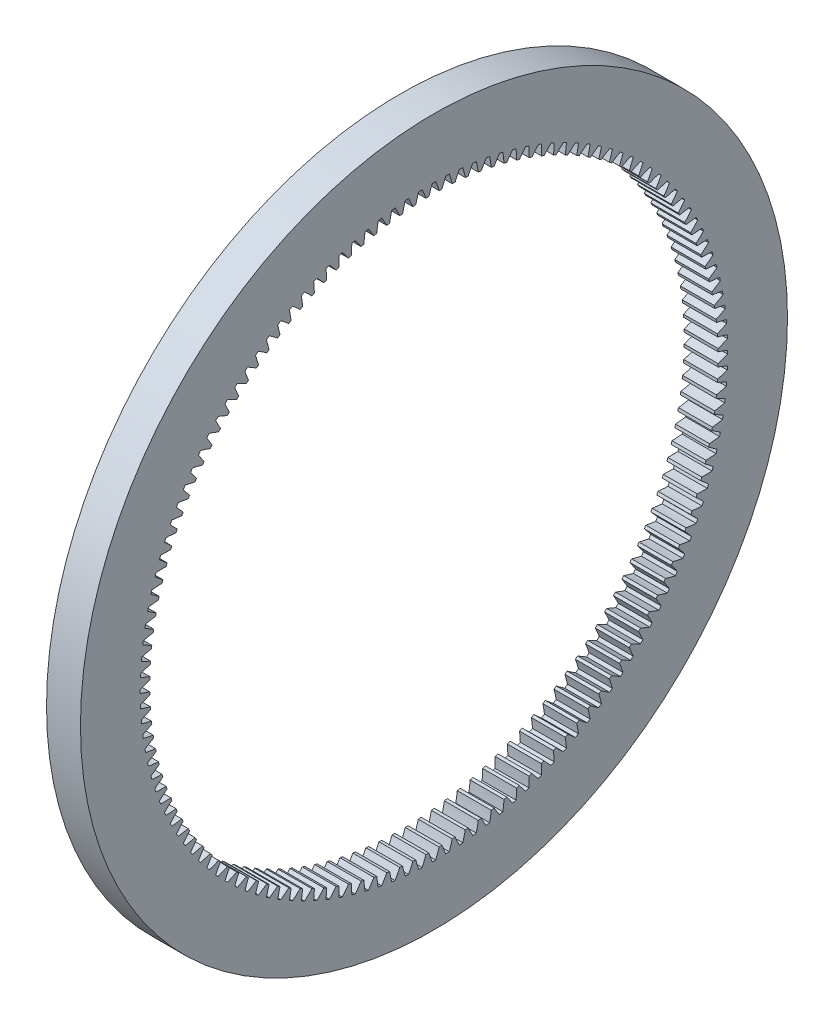
SolidWorks part; units mm, degrees
ref_plane "Plane1" through (0, 0, 0) normal (0, 0, 1) x (1, 0, 0)
ref_plane "Plane2" through (0, 0, 0) normal (0, 1, 0) x (1, 0, 0)
ref_plane "Plane3" through (0, 0, 0) normal (1, 0, 0) x (0, 0, -1)
sketch "HoldingSke" plane through (0, 0, 0) normal (0, 1, 0) x (1, 0, 0)
  line L0 (0, 0) -> (-0.4796, -0.4631)
  line L1 (-15, 0) -> (100, 0) construction
  line L2 (0, 0) -> (-2.1039, 2.3779)
  line L3 (0, 0) -> (-11.863, 4.5341)
  line L4 (0, 0) -> (-6.2122, 5.9991)
  line L5 (0, 0) -> (-23.7986, -8.8762)
  line L6 (0, 0) -> (-10.5278, -7.1032)
  line L7 (-2.1039, 2.3779) -> (3.3635, 27.1825)
  line L8 (-76.2, 3.8779) -> (-54.61, 3.8779)
  line L9 (-71.009, 38.7566) -> (-53.1078, 45.2721)
  line L10 (-76.2, 71.12) -> (104.1128, 71.12)
  line L11 (0, 0) -> (-12, 0)
  line L12 (-76.2, 101.6) -> (-76.147, 101.6)
  line L13 (24.9733, 27.94) -> (52.9518, 28.4284)
  line L14 (24.9733, 27.94) -> (24.9743, 27.94)
  line L15 (24.9733, 27.94) -> (100.4006, 29.5858)
  circle A0 centre (0, 0) radius 125
  circle A1 centre (0, 0) radius 12.7
  circle A2 centre (0, 0) radius 12.7
  dimension "Num_teeth" = 136
  dimension "Pitch_radius" = 180.3128
  dimension "Width" = 12
  dimension "Diameter" = 250
sketch "BasProSke" plane through (0, 0, 0) normal (0, 1, 0) x (1, 0, 0)
  line L0 (-10, 0) -> (60, 0) construction
  line L1 (0, 100.5) -> (0, 125)
  line L2 (0, 100.5) -> (12, 100.5)
  line L3 (12, 100.5) -> (12, 125)
  line L4 (12, 125) -> (0, 125)
  dimension "Thickness" = 12
  dimension "Diameter" = 250
revolve "Base-Revolve" add sketch "BasProSke" angle 360 about L0
sketch "TooCutSke" plane through (0, 0, 0) normal (1, 0, 0) x (0, 0, -1)
  line L3 (1.3106, 101.9916) -> (1.3106, 53.6633) construction
  line L4 (0, 0) -> (0, 59.563) construction
  line L5 (0, 0) -> (-1.5782, 68.3093) construction
  line L6 (-46.8474, 85.2044) -> (35.8402, 87.1149) construction
  circle A0 centre (0, 0) radius 102 construction
  circle A1 centre (0, 0) radius 103.876 construction
  circle A2 centre (0, 0) radius 86.2638 construction
  circle A3 centre (0, 0) radius 100.4746 construction
  arc A4 (1.818, 100.4582) -> (0.6125, 103.8742) centre (-46.8474, 85.2044) ccw
  arc A5 (1.818, 100.4582) -> (-1.818, 100.4582) centre (0, 0) ccw
  arc A6 (0.6125, 103.8742) -> (-0.6125, 103.8742) centre (0, 0) ccw
  arc A7 (-0.6125, 103.8742) -> (-1.818, 100.4582) centre (46.8474, 85.2044) ccw
extrude "ToothCut" cut sketch "TooCutSke" along normal through all
fillet "Breaks" [suppressed] radius 0.15
fillet "RootFillets" [suppressed] radius 0.376
pattern_circular "TeethCuts" count 136 every 2.647 about axis through (-10, 0, 0) along (1, 0, 0) of "RootFillets", "Breaks", "ToothCut"
sketch "草圖2" plane through (12, 0, 0) normal (1, 0, 0) x (0, 0, -1)
  circle A1 centre (0, 0) radius 125
  circle A2 centre (0, 0) radius 125
  dimension "D1" = 0
equation "' \"Module@HoldingSke\" = 6.35"
equation "' \"Num_teeth@HoldingSke\" = 24"
equation "' \"Ap@HoldingSke\" =  14.5"
equation "' \"Ap@HoldingSke\" = 14.5"
equation "' \"Width@HoldingSke\" = 12"
equation "' \"Diameter@HoldingSke\" = 8 * 25.4"
equation "' \"Show_teeth@HoldingSke\" = 100"
equation "' \"Backlash@HoldingSke\" = 0.009 * 25.4"
equation "' \"Addendum_fac@HoldingSke\" = 1.0"
equation "' \"Dedendum_fac@HoldingSke\" = 1.25"
equation "' \"Dedendum_add@HoldingSke\" = 0.00005 * 25.4"
equation "' \"Clearance_fac@HoldingSke\" = 0.25"
equation "\"Pitch@HoldingSke\" = 1 / \"Module@HoldingSke\" "
equation "\"Overcut_dia@TooCutSke\" = (\"Num_teeth@HoldingSke\" - 2 * \"Addendum_fac@HoldingSke\") / \"Pitch@HoldingSke\" - 0.002 * 25.4"
equation "\"Pitch_dia@TooCutSke\" = \"Num_teeth@HoldingSke\" / \"Pitch@HoldingSke\""
equation "\"Base_dia@TooCutSke\" = \"Num_teeth@HoldingSke\" / \"Pitch@HoldingSke\" * cos((\"Ap@HoldingSke\"  * 3.14159265 / 180)) * 0.90"
equation "\"Root_dia@TooCutSke\" = \"Num_teeth@HoldingSke\"  / \"Pitch@HoldingSke\" + 2 *  \"Dedendum_fac@HoldingSke\"/ \"Pitch@HoldingSke\" + \"Dedendum_add@HoldingSke\" * 2"
equation "\"Half_ang@TooCutSke\" = 180 / \"Num_teeth@HoldingSke\""
equation "\"Half_CT@TooCutSke\" = \"Num_teeth@HoldingSke\" / \"Pitch@HoldingSke\" * sin((3.14159265 / 2 / \"Num_teeth@HoldingSke\")) / 2 + 10 * \"Backlash@HoldingSke\" / 4"
equation "\"Flank_rad@TooCutSke\" = \"Num_teeth@HoldingSke\" / \"Pitch@HoldingSke\" / 4"
equation "\"Radius@RootFillets\"= \"Clearance_fac@HoldingSke\" / \"Pitch@HoldingSke\" + \"Dedendum_add@HoldingSke\""
equation "\"Break_rad@Breaks\" = 0.02 / \"Pitch@HoldingSke\" * 5"
equation "\"Num_teeth@TeethCuts\" = int( \"Show_teeth@HoldingSke\" ) + 1"
equation "\"Num_teeth@TeethCuts\" = ((sgn( \"Num_teeth@TeethCuts\" - \"Num_teeth@HoldingSke\" )-1)*( \"Num_teeth@TeethCuts\" - \"Num_teeth@HoldingSke\" ))/-2+ \"Num_teeth@HoldingSke\""
equation "\"Num_teeth@TeethCuts\" = ((sgn( \"Num_teeth@TeethCuts\" - 2.0)+1)*( \"Num_teeth@TeethCuts\" - 2.0))/2 +2.0"
equation "\"Angle@TeethCuts\" = 360.0 / \"Num_teeth@HoldingSke\""
equation "\"Diameter@BasProSke\" = \"Num_teeth@HoldingSke\"  / \"Pitch@HoldingSke\" + 2 *  \"Dedendum_fac@HoldingSke\"/ \"Pitch@HoldingSke\" + \"Dedendum_add@HoldingSke\" * 2 + 0.002 * 25.4"
equation "\"Diameter@BasProSke\" = ((sgn( \"Diameter@BasProSke\"  - \"Diameter@HoldingSke\" )+1)*( \"Diameter@BasProSke\"  - \"Diameter@HoldingSke\" ))/2 + \"Diameter@HoldingSke\""
equation "\"Inside_diameter@BasProSke\" =  (\"Num_teeth@HoldingSke\" - 2 * \"Addendum_fac@HoldingSke\") / \"Pitch@HoldingSke\" "
equation "\"Thickness@BasProSke\"  = \"Width@HoldingSke\""
